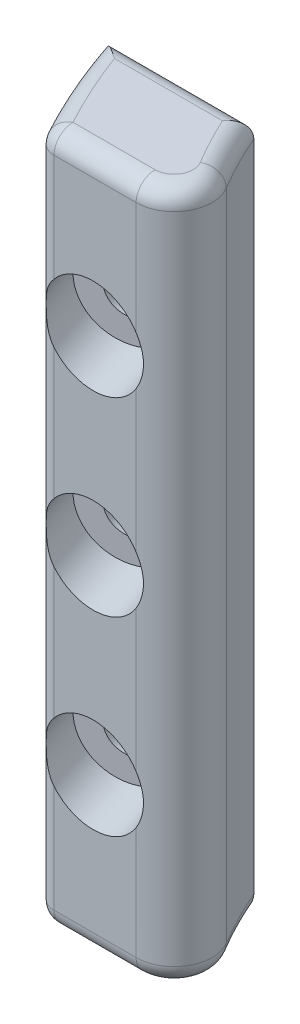
SolidWorks part; units mm, degrees
material "ABS"
ref_plane "Front Plane" through (0, 0, 0) normal (0, 0, 1) x (1, 0, 0)
ref_plane "Top Plane" through (0, 0, 0) normal (0, 1, 0) x (1, 0, 0)
ref_plane "Right Plane" through (0, 0, 0) normal (1, 0, 0) x (0, 0, -1)
sketch "Sketch1" plane through (0, 0, 0) normal (0, 1, 0) x (1, 0, 0)
  line L1 (0, 0) -> (7.15, 0)
  line L2 (0, 0) -> (0, 6)
  line L3 (0, 6) -> (7.15, 6)
  line L4 (7.15, 0) -> (7.15, 6)
  dimension "D1" = 7.15
  dimension "D2" = 6
extrude "BULK EXTRUDE" add sketch "Sketch1" along normal mid plane 36.4
sketch "Sketch2" plane through (0, 0, 0) normal (0, 1, 0) x (1, 0, 0)
  line L4 (0, 0) -> (7.15, 0)
  line L5 (7.15, 0) -> (7.15, 6)
  line L6 (7.15, 6) -> (0, 6)
  line L7 (0, 6) -> (0, 0)
  line L8 (0, 0) -> (2.6113, 0)
  line L10 (-0.0233, 6) -> (0, 6)
  line L11 (0, 6) -> (0, 0)
  arc A0 (-0.0233, 6) -> (2.6113, 0) centre (30.9, 16) ccw
  dimension "D2" = 65
  dimension "D1" = 30.9
  dimension "D3" = 16
  dimension "D4" = 0
extrude "OUTSIDE ROUNDING" cut sketch "Sketch2" along normal through all both and the other way through all contours A0 L11 L8 region at (0.8331, 0, -1.8806)
sketch "Sketch3" plane through (0, 0, 0) normal (0, 1, 0) x (1, 0, 0)
  line L0 (7.15, 6) -> (7.7146, 6)
  line L1 (7.15, 0) -> (11.3664, 0)
  line L4 (0, 0) -> (7.15, 0)
  line L5 (7.15, 0) -> (7.15, 6)
  line L6 (7.15, 6) -> (0, 6)
  line L7 (0, 6) -> (0, 0)
  line L9 (7.15, 0) -> (7.15, 6)
  arc A0 (7.7146, 6) -> (11.3664, 0) centre (30.9, 16) ccw
  dimension "D1" = 50.5
  dimension "D2" = 0
extrude "INNER ROUNDING FOR HOLDING THE PCBs" add sketch "Sketch3" along normal mid plane 36.4
ref_plane "TANGENT PLANE ON OUTSIDE" through (1.7467, 0, -0.5693) normal (-0.9508, 0, 0.3099) x (0.3099, 0, 0.9508)
ref_plane "PERPENDICULAR PLANE" through (-1.7467, 0, -5.3589) normal (-0.3099, 0, -0.9508) x (0, -1, 0)
ref_plane "COUNTERBORE PLANE" through (-0.5071, 0, -1.5558) normal (0.3099, 0, 0.9508) x (0, -1, 0)
sketch "Sketch5" plane through (-0.8784, 0, -5.6419) normal (0.3099, 0, 0.9508) x (0.9508, 0, -0.3099)
  circle A0 centre (4.0867, 0) radius 1.25
  circle A1 centre (4.0867, 10) radius 1.25
  circle A2 centre (4.0867, -10) radius 1.25
  dimension "D1" = 2.5
  dimension "D2" = 5
  dimension "D3" = 10
  dimension "D4" = 10
extrude "M2 CLEARANCE HOLES" cut sketch "Sketch5" along normal through all
sketch "Sketch6" plane through (-0.5071, 0, -1.5558) normal (0.3099, 0, 0.9508) x (0, -1, 0)
  circle A0 centre (-10, 5) radius 2.5
  circle A1 centre (0, 5) radius 2.5
  circle A2 centre (10, 5) radius 2.5
  dimension "D1" = 5
extrude "M2 COUNTERBORE CUTS" cut sketch "Sketch6" along normal through all
fillet "Fillet1" radius 2 1 edges at (11.3664, 0, 0)
fillet "Fillet2" radius 1 13 edges at (3.8573, -18.2, -6) (1.1576, -18.2, -2.8989) (5.0663, -18.2, 0) (9.2613, -18.2, -1.0139) (8.4267, -18.2, -4.4886) (1.1576, 18.2, -2.8989) (3.8573, 18.2, -6) (8.4267, 18.2, -4.4886) (9.2613, 18.2, -1.0139) (5.0663, 18.2, 0) (2.6113, 0, 0) (0, -18.2, -5.9641) (0, 18.2, -5.9641)
